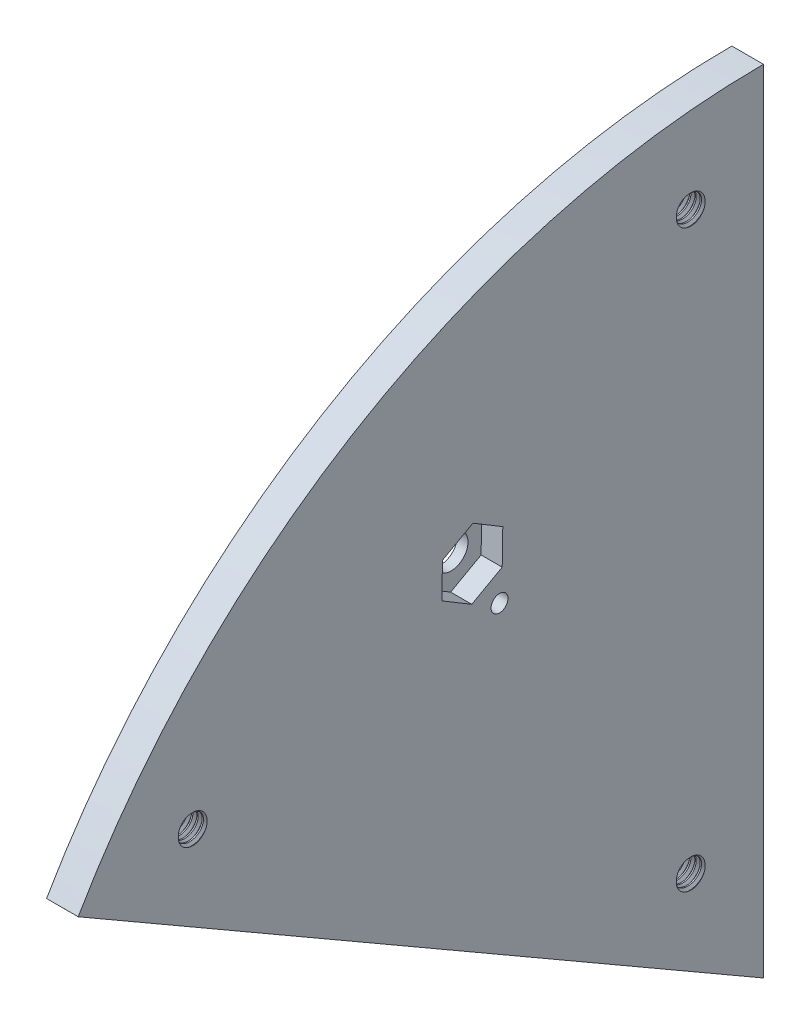
SolidWorks part; units mm, degrees
ref_plane "Front Plane" through (0, 0, 0) normal (0, 0, 1) x (1, 0, 0)
ref_plane "Top Plane" through (0, 0, 0) normal (0, 1, 0) x (1, 0, 0)
ref_plane "Right Plane" through (0, 0, 0) normal (1, 0, 0) x (0, 0, -1)
sketch "Sketch1" plane through (0, 0, 0) normal (0, 0, 1) x (1, 0, 0)
  line L0 (0, 0) -> (0, 150)
sketch "Sketch2" plane through (0, 0, 0) normal (0, 1, 0) x (1, 0, 0)
  line L0 (-55.1261, 0) -> (52.6623, 0)
revolve "Revolve-Thin1" add sketch "Sketch1" angle 60 about L0
sketch "Sketch3" plane through (167.0171, 0, 0) normal (-1, 0, 0) x (0, 0, 1)
  point P0 (-0.3008, -0.4529)
sketch "Sketch4" plane through (6, 0, 0) normal (1, 0, 0) x (0, 0, -1)
  circle A0 centre (-50.0316, 86.5479) radius 1.6
extrude "Cut-Extrude1" cut sketch "Sketch4" against normal blind 6
sketch "Sketch6" plane through (6, 0, 0) normal (1, 0, 0) x (0, 0, -1)
  circle A0 centre (-55.1894, 95.6005) radius 3.175
extrude "Cut-Extrude2" cut sketch "Sketch6" against normal blind 6
sketch "Sketch7" plane through (6, 0, 0) normal (1, 0, 0) x (0, 0, -1)
  line L1 (-60.9632, 92.3926) -> (-55.2982, 88.9963)
  line L2 (-55.2982, 88.9963) -> (-49.5244, 92.2042)
  line L3 (-49.5244, 92.2042) -> (-49.4156, 98.8084)
  line L4 (-49.4156, 98.8084) -> (-55.0806, 102.2047)
  line L5 (-55.0806, 102.2047) -> (-60.8544, 98.9968)
  line L6 (-60.8544, 98.9968) -> (-60.9632, 92.3926)
  circle A0 centre (-55.1894, 95.6005) radius 5.7202 construction
extrude "Cut-Extrude3" cut sketch "Sketch7" against normal blind 4
sketch "Sketch10" plane through (6, 0, 0) normal (1, 0, 0) x (0, 0, -1)
  line L0 (0, 0) -> (0, 150) construction
  line L1 (0, 0) -> (-129.9038, 75) construction
  circle A0 centre (0, 0) radius 134
sketch "Sketch8" plane through (0, 0, 0) normal (-1, 0, 0) x (0, 0, 1)
  line L0 (0, 0) -> (129.9038, 75) construction
  line L2 (0, 0) -> (0, 150) construction
  circle A0 centre (108.4123, 78.7577) radius 3
  circle A1 centre (14, 133.2666) radius 3
  circle A2 centre (14, 24.2487) radius 3
  dimension "D2" = 14
  dimension "D3" = 14
  dimension "D4" = 14
  dimension "D1" = 14
hole_wizard "M6x1.0 Tapped Hole1" positions "Sketch11" profile "Sketch12" tap size "M6x1.0" standard "ANSI Metric"
sketch "Sketch11" plane through (6, 0, 0) normal (1, 0, 0) x (0, 0, -1)
  point P0 (-14, 133.2666)
  point P3 (-108.4123, 78.7577)
  point P6 (-14, 24.2487)
sketch "Sketch12" plane through (6, 133.2666, 14) normal (0, 1, 0) x (0, 0, -1)
  line L0 (0, 0) -> (0, 16.5022)
  line L1 (0, 16.5022) -> (2.5, 15)
  line L2 (2.5, 15) -> (2.5, 0)
  line L5 (2.5, 0) -> (0, 0)
  line L10 (0, 16.5022) -> (-2.5, 15) construction
  line L11 (0, -6.35) -> (0, 107.95) construction
  dimension "Tap Drill Dia." = 5
  dimension "Tap Drill Depth" = 15
  dimension "Drill Angle" = 118
thread "Thread1" pitch 1 start angle 0, offset 1, length 10, pitch 1, diameter 5
ref_plane "Plane2" through (7, 78.7577, 110.9123) normal (0, -1, 0) x (0, 0, 1)
sketch "Thread Profile2" plane through (7, 78.7577, 110.9123) normal (0, -1, 0) x (0, 0, 1)
  line L0 (0, 0) -> (0, 1) construction
  line L1 (0, 0) -> (0.5413, 0.3125)
  line L2 (0.5413, 0.3125) -> (0.5413, 0.4375)
  line L3 (0.5413, 0.4375) -> (0, 0.75)
  line L4 (0.5413, 0.375) -> (0, 0.375) construction
  line L11 (0, 0) -> (0, 0.75)
  point P2 (0, 0)
  dimension "Pitch" = 1
  dimension "Profile_Angle" = 60
  dimension "Profile_Land" = 0.125
  dimension "Profile_Height" = 0.5413
thread "Thread2" pitch 1 profile "Thread Profile3" start angle 0, offset 1, length 10, pitch 1, diameter 5
ref_plane "Plane3" through (7, 133.2666, 16.5) normal (0, -1, 0) x (0, 0, 1)
sketch "Thread Profile3" plane through (7, 133.2666, 16.5) normal (0, -1, 0) x (0, 0, 1)
  line L0 (0, 0) -> (0, 1) construction
  line L1 (0, 0) -> (0.5413, 0.3125)
  line L2 (0.5413, 0.3125) -> (0.5413, 0.4375)
  line L3 (0.5413, 0.4375) -> (0, 0.75)
  line L4 (0.5413, 0.375) -> (0, 0.375) construction
  line L11 (0, 0) -> (0, 0.75)
  point P2 (0, 0)
  dimension "Pitch" = 1
  dimension "Profile_Angle" = 60
  dimension "Profile_Land" = 0.125
  dimension "Profile_Height" = 0.5413
thread "Thread3" pitch 1 profile "Thread Profile4" start angle 0, offset 1, length 10, pitch 1, diameter 5
ref_plane "Plane4" through (7, 24.2487, 16.5) normal (0, -1, 0) x (0, 0, 1)
sketch "Thread Profile4" plane through (7, 24.2487, 16.5) normal (0, -1, 0) x (0, 0, 1)
  line L0 (0, 0) -> (0, 1) construction
  line L1 (0, 0) -> (0.5413, 0.3125)
  line L2 (0.5413, 0.3125) -> (0.5413, 0.4375)
  line L3 (0.5413, 0.4375) -> (0, 0.75)
  line L4 (0.5413, 0.375) -> (0, 0.375) construction
  line L11 (0, 0) -> (0, 0.75)
  point P2 (0, 0)
  dimension "Pitch" = 1
  dimension "Profile_Angle" = 60
  dimension "Profile_Land" = 0.125
  dimension "Profile_Height" = 0.5413
